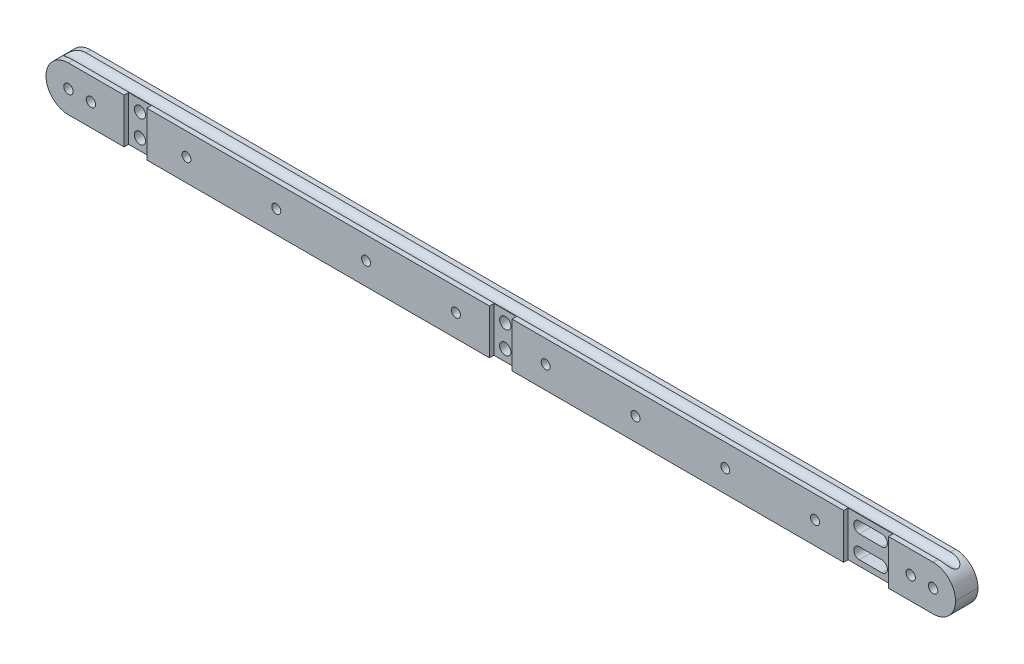
SolidWorks part; units mm, degrees
material "AISI 316 Barre d'acier inoxydable recuit (SS)"
ref_plane "Plan de face" through (0, 0, 0) normal (0, 0, 1) x (1, 0, 0)
ref_plane "Plan de dessus" through (0, 0, 0) normal (0, 1, 0) x (1, 0, 0)
ref_plane "Plan de droite" through (0, 0, 0) normal (1, 0, 0) x (0, 0, -1)
sketch "Esquisse1" plane through (0, 0, 0) normal (0, 0, 1) x (1, 0, 0)
  line L0 (0, 10) -> (405.15, 10) construction
  line L1 (0, 20) -> (405.15, 20) construction
  line L2 (0, 20) -> (0, 0)
  line L3 (0, 0) -> (405.15, 0) construction
  line L4 (405.15, 20) -> (405.15, 0)
  line L5 (202.575, 20) -> (202.575, 0) construction
  line L6 (0, 20) -> (60, 20)
  line L7 (405.15, 20) -> (385.15, 20)
  line L8 (60, 20) -> (385.15, 20)
  line L9 (81.7, 18) -> (88.9319, 18) construction
  line L10 (405.15, 0) -> (385.15, 0)
  line L11 (0, 0) -> (60, 0)
  line L12 (81.7, 2) -> (88.9319, 2) construction
  line L13 (385.15, 0) -> (60, 0)
  line L14 (365.3, 20) -> (365.3, 0) construction
  line L15 (360.3, 15) -> (370.3, 15) construction
  line L16 (360.3, 17.5) -> (370.3, 17.5)
  line L17 (360.3, 12.5) -> (370.3, 12.5)
  line L18 (360.3, 5) -> (370.3, 5) construction
  line L19 (360.3, 2.5) -> (370.3, 2.5)
  line L20 (360.3, 7.5) -> (370.3, 7.5)
  circle A2 centre (385.15, 10) radius 2 construction
  circle A3 centre (395.15, 10) radius 2 construction
  circle A4 centre (202.575, 15) radius 2.5
  circle A40 centre (10, 10) radius 2 construction
  circle A41 centre (20, 10) radius 2 construction
  circle A42 centre (202.575, 5) radius 2.5
  circle A44 centre (365.3, 5) radius 2.5 construction
  circle A45 centre (39.85, 5) radius 2.5
  circle A46 centre (39.85, 15) radius 2.5
  arc A47 (360.3, 17.5) -> (360.3, 12.5) centre (360.3, 15) ccw
  arc A48 (370.3, 12.5) -> (370.3, 17.5) centre (370.3, 15) ccw
  arc A49 (360.3, 2.5) -> (360.3, 7.5) centre (360.3, 5) cw
  arc A50 (370.3, 7.5) -> (370.3, 2.5) centre (370.3, 5) cw
  circle A51 centre (222.575, 10) radius 2
  circle A52 centre (262.575, 10) radius 2
  circle A53 centre (302.575, 10) radius 2
  circle A54 centre (342.575, 10) radius 2
  circle A55 centre (182.575, 10) radius 2
  circle A56 centre (142.575, 10) radius 2
  circle A57 centre (102.575, 10) radius 2
  circle A58 centre (62.575, 10) radius 2
  point P36 (365.3, 15)
  point P45 (365.3, 5)
  dimension "D3" = 10
  dimension "D4" = 5
  dimension "D7" = 4
  dimension "D9" = 162.725
  dimension "D10" = 5
  dimension "D11" = 162.725
  dimension "D12" = 20
  dimension "D13" = 60
  dimension "D14" = 10
  dimension "D15" = 10
  dimension "D16" = 5
  dimension "D18" = 10
  dimension "D19" = 10
  dimension "D5" = 5
  dimension "D20" = 4
  dimension "D22" = 4
  dimension "D23" = 40
  dimension "D1" = 20
  dimension "D2" = 405.15
  dimension "D6" = 10
  dimension "D8" = 10
  dimension "D17" = 2
  dimension "D21" = 20
extrude "Boss.-Extru.1" add sketch "Esquisse1" along normal blind 10 contours L2 L11 L10 L4 L7 L6 A4 A42 region at (200.4847, 10, 0)
fillet "Congé1" radius 10 4 edges at (0, 0, 5) (0, 20, 5) (405.15, 0, 5) (405.15, 20, 5)
sketch "Esquisse3" plane through (0, 0, 10) normal (0, 0, 1) x (1, 0, 0)
  line L1 (202.575, 20) -> (202.575, 0) construction
  line L5 (10, 0) -> (395.15, 0) construction
  line L6 (202.575, 10) -> (405.15, 10) construction
  point P0 (385.15, 10)
  point P2 (395.15, 10)
  point P21 (10, 10)
  point P22 (20, 10)
  dimension "D1" = 10
  dimension "D2" = 10
hole_wizard "Trou taraudé M5x0.81" positions "Esquisse3" profile "Esquisse4" tap size "M5x0.8" standard "Ansi Metric" end condition through all
cosmetic thread "Filetage de perçage1" parameters "D1"=10, "D2"=5
cosmetic thread "Filetage de perçage2" parameters "D1"=10, "D2"=5
sketch "Esquisse4" plane through (385.15, 10, 10) normal (1, 0, 0) x (0, -1, 0)
  line L0 (0, 0) -> (0, 10)
  line L1 (0, 10) -> (2.1, 10)
  line L2 (2.1, 10) -> (2.1, 0)
  line L5 (2.1, 0) -> (0, 0)
  line L11 (0, -6.35) -> (0, 107.95) construction
  dimension "Diamètre du trou pour taraudage jusqu'au prochain" = 4.2
  dimension "Profondeur du trou pour taraudage jusqu'au prochain" = 10
cosmetic thread "Filetage de perçage5" parameters "D1"=10, "D2"=5
cosmetic thread "Filetage de perçage6" parameters "D1"=10, "D2"=5
sketch "Esquisse5" plane through (0, 0, 10) normal (0, 0, 1) x (1, 0, 0)
  line L1 (365.3, 20) -> (365.3, 0) construction
  line L3 (395.15, 0) -> (10, 0) construction
  line L4 (207.625, 0) -> (197.525, 0)
  line L6 (202.575, 20) -> (202.575, 0) construction
  line L7 (197.525, 0) -> (197.525, 20)
  line L8 (197.525, 20) -> (207.625, 20)
  line L9 (207.625, 20) -> (207.625, 0)
  line L10 (395.15, 20) -> (10, 20) construction
  line L11 (355.3, 20) -> (375.3, 20)
  line L12 (375.3, 20) -> (375.3, 0)
  line L13 (375.3, 0) -> (355.3, 0)
  line L14 (355.3, 0) -> (355.3, 20)
  line L15 (44.9, 20) -> (34.8, 20)
  line L16 (44.9, 0) -> (44.9, 20)
  line L17 (34.8, 0) -> (44.9, 0)
  line L18 (34.8, 20) -> (34.8, 0)
  line L19 (39.85, 15) -> (39.85, 5) construction
  line L20 (360.3, 17.5) -> (370.3, 17.5) construction
  point P11 (365.3, 14.5013)
  point P29 (365.3, 17.5)
  dimension "D1" = 10.1
  dimension "D2" = 10.1
  dimension "D3" = 20
  dimension "D4" = 10.1
  dimension "D5" = 10.1
  dimension "D6" = 10.1
extrude "Enlèv. mat.-Extru.1" cut sketch "Esquisse5" against normal blind 2
sketch "Esquisse6" plane through (0, 0, 0) normal (1, 0, 0) x (0, 0, -1)
  line L0 (-10, 10) -> (0, 10) construction
  line L1 (-5, 10) -> (-5, 21) construction
  line L2 (-10, 20) -> (0, 20) construction
  circle A0 centre (-5, 21) radius 3
  dimension "D1" = 6
  dimension "D2" = 1
extrude "Enlèv. mat.-Extru.3" cut sketch "Esquisse6" along normal through all
